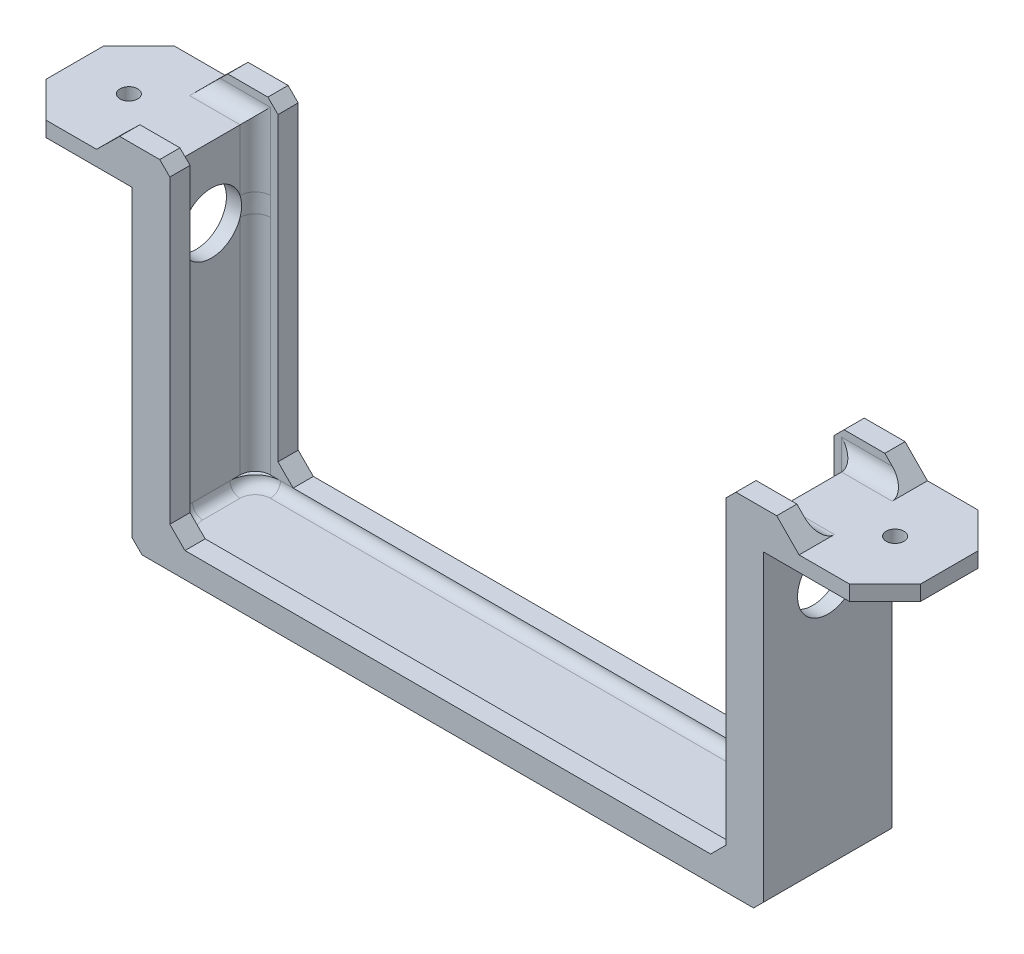
SolidWorks part; units mm, degrees
ref_plane "Front Plane" through (0, 0, 0) normal (0, 0, 1) x (1, 0, 0)
ref_plane "Top Plane" through (0, 0, 0) normal (0, 1, 0) x (1, 0, 0)
ref_plane "Right Plane" through (0, 0, 0) normal (1, 0, 0) x (0, 0, -1)
sketch "Sketch1" plane through (0, 0, 0) normal (0, 1, 0) x (1, 0, 0)
  line L1 (-62.5, 12.7) -> (62.5, 12.7)
  line L2 (-62.5, 12.7) -> (-62.5, -12.7)
  line L3 (-62.5, -12.7) -> (62.5, -12.7)
  line L4 (62.5, 12.7) -> (62.5, -12.7)
  line L5 (-62.5, 12.7) -> (62.5, -12.7) construction
  line L6 (-62.5, -12.7) -> (62.5, 12.7) construction
  point P0 (0, 0)
  dimension "D1" = 25.4
  dimension "D2" = 125
extrude "Boss-Extrude1" add sketch "Sketch1" along normal blind 5
sketch "Sketch2" plane through (0, 5, 0) normal (0, 1, 0) x (1, 0, 0)
  line L0 (62.5, 12.7) -> (-62.5, 12.7) construction
  line L1 (-59.5, 8.7) -> (59.5, 8.7)
  line L2 (-59.5, 8.7) -> (-59.5, -8.7)
  line L3 (-59.5, -8.7) -> (59.5, -8.7)
  line L4 (59.5, 8.7) -> (59.5, -8.7)
  line L5 (-59.5, 8.7) -> (59.5, -8.7) construction
  line L6 (-59.5, -8.7) -> (59.5, 8.7) construction
  line L7 (-62.5, 12.7) -> (-62.5, -12.7) construction
  point P0 (0, 0)
  dimension "D1" = 4
  dimension "D2" = 3
extrude "Cut-Extrude1" cut sketch "Sketch2" against normal blind 2
fillet "Fillet1" radius 5 4 edges at (59.5, 4, 8.7) (59.5, 4, -8.7) (-59.5, 4, 8.7) (-59.5, 4, -8.7)
sketch "Sketch3" plane through (0, 5, 0) normal (0, 1, 0) x (1, 0, 0)
  line L0 (-62.5, -12.7) -> (62.5, -12.7) construction
  line L1 (62.5, 12.7) -> (59.5, 12.7)
  line L2 (62.5, 12.7) -> (62.5, -12.7)
  line L3 (62.5, -12.7) -> (59.5, -12.7)
  line L4 (59.5, 12.7) -> (59.5, -12.7)
  line L6 (-62.5, 12.7) -> (-59.5, 12.7)
  line L7 (-62.5, 12.7) -> (-62.5, -12.7)
  line L8 (-62.5, -12.7) -> (-59.5, -12.7)
  line L9 (-59.5, 12.7) -> (-59.5, -12.7)
  point P12 (-59.5, -12.7)
  point P13 (59.5, -12.7)
extrude "Boss-Extrude2" add sketch "Sketch3" along normal blind 60
chamfer "Chamfer1" distance 2 angle 45 2 edges at (-62.5, 0, 0) (62.5, 0, 0)
sketch "Sketch4" plane through (62.5, 0, 0) normal (1, 0, 0) x (0, 0, -1)
  line L1 (-12.7, 65) -> (12.7, 65) construction
  circle A0 centre (0, 51) radius 6
  dimension "D1" = 14
  dimension "D2" = 12
extrude "Cut-Extrude3" cut sketch "Sketch4" against normal blind 135.4
sketch "Sketch5" plane through (-62.5, 0, 0) normal (-1, 0, 0) x (0, 0, 1)
  line L0 (12.7, 65) -> (12.7, 2) construction
  line L1 (-12.7, 65) -> (12.7, 65)
  line L2 (-12.7, 65) -> (-12.7, 62)
  line L3 (-12.7, 62) -> (12.7, 62)
  line L4 (12.7, 65) -> (12.7, 62)
  dimension "D1" = 3
extrude "Boss-Extrude3" add sketch "Sketch5" along normal blind 24
sketch "Sketch6" plane through (62.5, 0, 0) normal (1, 0, 0) x (0, 0, -1)
  line L0 (12.7, 65) -> (12.7, 2) construction
  line L1 (-12.7, 65) -> (12.7, 65)
  line L2 (-12.7, 65) -> (-12.7, 62)
  line L3 (-12.7, 62) -> (12.7, 62)
  line L4 (12.7, 65) -> (12.7, 62)
  dimension "D1" = 3
extrude "Boss-Extrude4" add sketch "Sketch6" along normal blind 24
sketch "Sketch9" plane through (0, 65, 0) normal (0, 1, 0) x (1, 0, 0)
  line L0 (86.5, 12.7) -> (86.5, -12.7) construction
  circle A0 centre (75.8, 0) radius 1.75
  circle A1 centre (-75.8, 0) radius 1.75
  dimension "D1" = 3.5
  dimension "D2" = 3.5
  dimension "D3" = 151.6
  dimension "D4" = 10.7
extrude "Cut-Extrude4" cut sketch "Sketch9" against normal blind 4
chamfer "Chamfer2" distance 7 angle 45 4 edges at (86.5, 63.5, 12.7) (86.5, 63.5, -12.7) (-86.5, 63.5, 12.7) (-86.5, 63.5, -12.7)
sketch "Sketch10" plane through (0, 0, 12.7) normal (0, 0, 1) x (1, 0, 0)
  line L0 (-69.5, 65) -> (-64.9249, 69.5)
  line L1 (-79.5, 65) -> (-59.5, 65) construction
  line L2 (-64.9249, 69.5) -> (-55, 69.5)
  line L3 (-55, 69.5) -> (-55, 5)
  line L4 (-59.5, 5) -> (59.5, 5) construction
  line L5 (-69.5, 65) -> (-59.5, 65)
  line L6 (-59.5, 65) -> (-59.5, 5)
  line L7 (-59.5, 5) -> (-55, 5)
  line L8 (69.5, 65) -> (65.0739, 69.5)
  line L9 (59.5, 65) -> (79.5, 65) construction
  line L10 (65.0739, 69.5) -> (55, 69.5)
  line L11 (55, 69.5) -> (55, 5)
  line L12 (55, 5) -> (59.5, 5)
  line L13 (59.5, 5) -> (59.5, 65)
  line L14 (59.5, 65) -> (69.5, 65)
  dimension "D1" = 4.5
  dimension "D2" = 4.5
  dimension "D3" = 4.5
  dimension "D4" = 4.5
extrude "Boss-Extrude5" add sketch "Sketch10" against normal blind 4
sketch "Sketch11" plane through (0, 0, -12.7) normal (0, 0, -1) x (-1, 0, 0)
  line L0 (-69.5, 65) -> (-65.0739, 69.5)
  line L1 (-79.5, 65) -> (-59.5, 65) construction
  line L2 (-65.0739, 69.5) -> (-55, 69.5)
  line L3 (-55, 69.5) -> (-55, 5)
  line L4 (-55, 5) -> (-59.5, 5)
  line L5 (-59.5, 5) -> (-59.5, 65)
  line L6 (-59.5, 65) -> (-69.5, 65)
  line L7 (69.5, 65) -> (64.9249, 69.5)
  line L8 (64.9249, 69.5) -> (55, 69.5)
  line L9 (55, 69.5) -> (55, 5)
  line L10 (55, 5) -> (59.5, 5)
  line L11 (59.5, 5) -> (59.5, 65)
  line L12 (59.5, 65) -> (69.5, 65)
extrude "Boss-Extrude6" add sketch "Sketch11" against normal blind 4
chamfer "Chamfer3" distance 2 angle 45 4 edges at (-55, 69.5, -10.7) (-55, 69.5, 10.7) (55, 69.5, -10.7) (55, 69.5, 10.7)
chamfer "Chamfer4" distance 3 angle 45 4 edges at (55, 5, -10.7) (55, 5, 10.7) (-55, 5, -10.7) (-55, 5, 10.7)
fillet "Fillet5" radius 2 8 edges at (-58.0355, 3, 7.2355) (-59.5, 3, 0) (-58.0355, 3, -7.2355) (0, 3, -8.7) (58.0355, 3, -7.2355) (59.5, 3, 0) (58.0355, 3, 7.2355) (0, 3, 8.7)
fillet "Fillet6" radius 3 8 edges at (64.5, 65, -8.7) (64.5, 65, 8.7) (-64.5, 65, 8.7) (-64.5, 65, -8.7) (-59.5, 35, -8.7) (-59.5, 35, 8.7) (59.5, 35, 8.7) (59.5, 35, -8.7)
